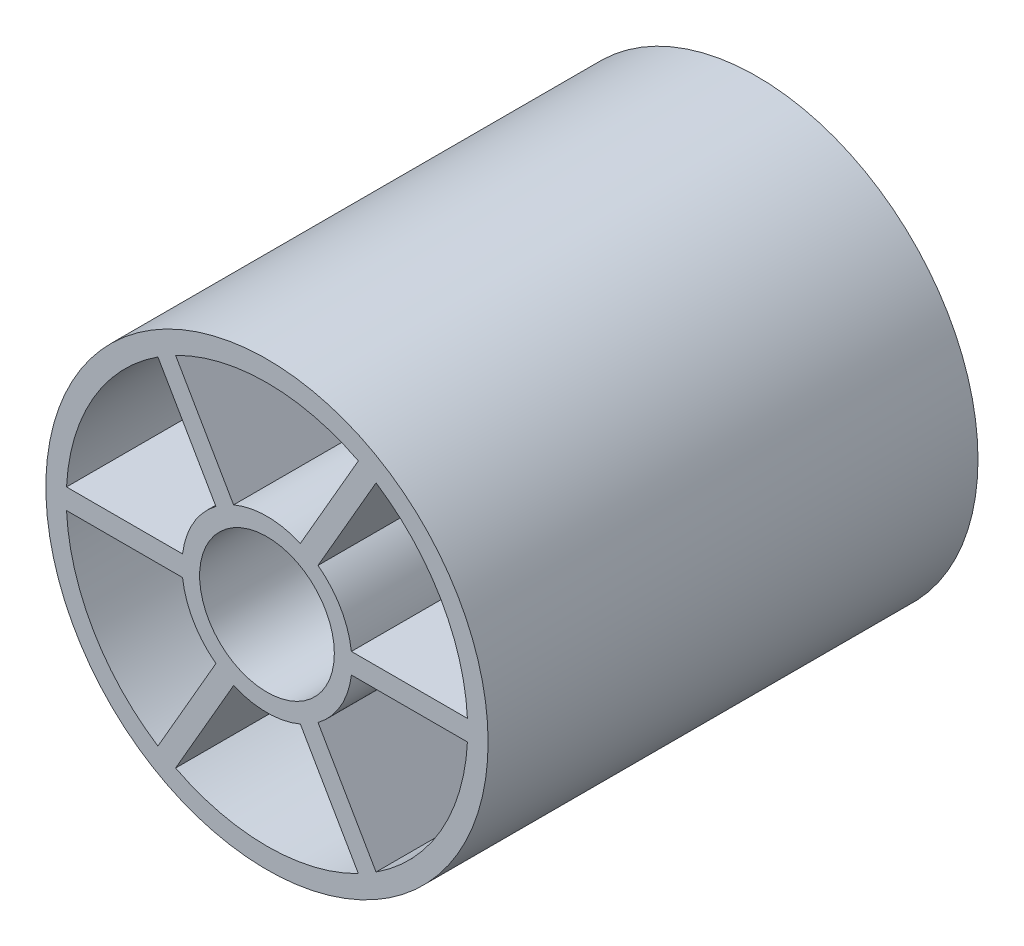
SolidWorks part; units mm, degrees
material "PET"
ref_plane "Front Plane" through (0, 0, 0) normal (0, 0, 1) x (1, 0, 0)
ref_plane "Top Plane" through (0, 0, 0) normal (0, 1, 0) x (1, 0, 0)
ref_plane "Right Plane" through (0, 0, 0) normal (1, 0, 0) x (0, 0, -1)
sketch "Sketch1" plane through (0, 0, 0) normal (0, 0, 1) x (1, 0, 0)
  circle A0 centre (0, 0) radius 32.5
  circle A1 centre (0, 0) radius 29.5
  dimension "D1" = 65
  dimension "D2" = 3
extrude "Boss-Extrude1" add sketch "Sketch1" along normal up to surface (72 mm away)
sketch "Sketch2" plane through (0, 0, 0) normal (0, 0, 1) x (1, 0, 0)
  line L0 (-29.4618, -1.5) -> (29.4618, -1.5)
  line L1 (-29.4618, 1.5) -> (29.4618, 1.5)
  line L2 (0, 0) -> (29.5, 0) construction
  circle A0 centre (0, 0) radius 29.5 construction
  arc A1 (-29.4618, 1.5) -> (-29.4618, -1.5) centre (0, 0) ccw
  arc A2 (29.4618, -1.5) -> (29.4618, 1.5) centre (0, 0) ccw
  dimension "D1" = 3
extrude "Boss-Extrude2" add sketch "Sketch2" along normal through all
ref_axis "Axis1" through (0, 0, -3.6) along (0, 0, 1)
pattern_circular "CirPattern1" count 3 every 60 about axis through (0, 0, -3.6) along (0, 0, 1) of "Boss-Extrude2"
sketch "Sketch6" plane through (0, 0, 0) normal (0, 0, 1) x (1, 0, 0)
  circle A1 centre (0, 0) radius 9.5
  circle A2 centre (0, 0) radius 9.5
  dimension "D1" = 0
sketch "Sketch7" plane through (0, 0, 0) normal (0, 0, 1) x (1, 0, 0)
  circle A0 centre (0, 0) radius 12.5
  circle A1 centre (0, 0) radius 9.5 construction
  circle A2 centre (0, 0) radius 9.5 construction
  dimension "D1" = 3
extrude "Boss-Extrude5" add sketch "Sketch7" along normal through all
sketch "Sketch9" plane through (0, 0, 0) normal (0, 0, 1) x (1, 0, 0)
  circle A0 centre (0, 0) radius 9.9
  circle A1 centre (0, 0) radius 9.5 construction
  circle A2 centre (0, 0) radius 9.5 construction
  dimension "D1" = 0.4
extrude "Cut-Extrude4" cut sketch "Sketch9" along normal through all
